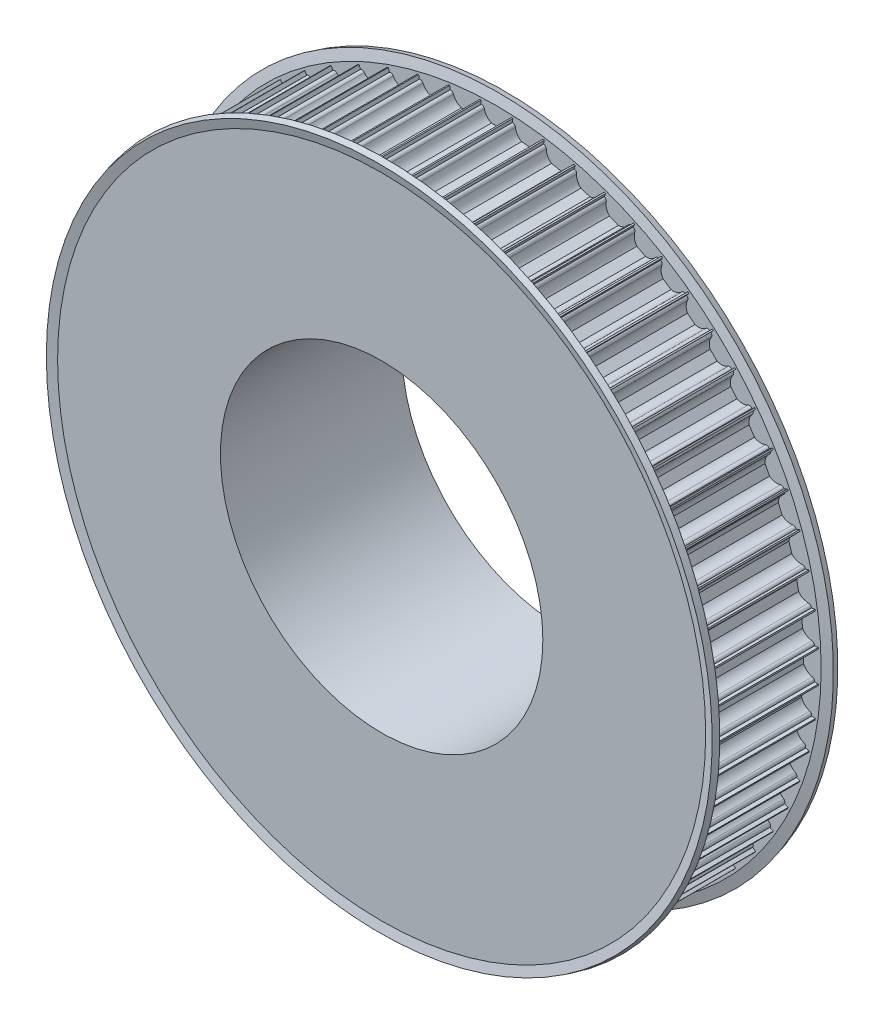
SolidWorks part; units mm, degrees
ref_plane "Front Plane" through (0, 0, 0) normal (0, 0, 1) x (1, 0, 0)
ref_plane "Top Plane" through (0, 0, 0) normal (0, 1, 0) x (1, 0, 0)
ref_plane "Right Plane" through (0, 0, 0) normal (1, 0, 0) x (0, 0, -1)
sketch "Sketch1" plane through (0, 0, 0) normal (1, 0, 0) x (0, 0, -1)
  line L0 (0, 0) -> (38.5259, 0) construction
  line L1 (0, 40) -> (45, 40)
  line L2 (45, 40) -> (45, 55.5)
  line L3 (45, 55.5) -> (30, 55.5)
  line L4 (30, 55.5) -> (30, 80)
  line L5 (30, 80) -> (0, 80)
  line L6 (0, 80) -> (0, 40)
  dimension "D1" = 80
  dimension "D2" = 40
  dimension "D3" = 30
  dimension "D4" = 15
  dimension "D5" = 15.5
revolve "Revolve1" add sketch "Sketch1" angle 360 about L0
sketch "Sketch2" plane through (0, 0, 0) normal (0, 0, 1) x (1, 0, 0)
  line L0 (-3.6742, 79) -> (-3.75, 79)
  line L1 (-3.75, 79) -> (-3.75, 81)
  line L2 (-3.75, 81) -> (3.75, 81)
  line L3 (3.75, 81) -> (3.75, 79)
  line L4 (3.6742, 79) -> (3.75, 79)
  line L5 (-1.199, 76.25) -> (1.199, 76.25)
  arc A0 (2.9394, 78.4) -> (1.199, 76.25) centre (0, 79) cw
  arc A1 (2.9394, 78.4) -> (3.6742, 79) centre (3.6742, 78.25) cw
  arc A2 (-2.9394, 78.4) -> (-3.6742, 79) centre (-3.6742, 78.25) ccw
  arc A3 (-1.199, 76.25) -> (-2.9394, 78.4) centre (0, 79) cw
  point P3 (0, 81)
  point P11 (3, 79)
  point P14 (-3, 79)
  dimension "D1" = 3
  dimension "D5" = 0.75
  dimension "D2" = 79
  dimension "D3" = 7.5
  dimension "D4" = 2
  dimension "D6" = 2.75
extrude "Cut-Extrude1" cut sketch "Sketch2" against normal up to next
pattern_circular "CirPattern1" count 64 over 360 about axis through (0, 0, 0) along (0, 0, 1) of "Cut-Extrude1"
sketch "Sketch3" plane through (0, 0, 0) normal (1, 0, 0) x (0, 0, -1)
  line L0 (15, -40.9775) -> (15, -11.3999) construction
  line L1 (30, -40.9775) -> (0, -40.9775) construction
  line L2 (30, -11.3999) -> (0, -11.3999) construction
  line L3 (30, 55.5) -> (30, 80.4056)
  line L4 (30, -32.718) -> (30, -30.2873) construction
  line L5 (30, -55.5) -> (30, 55.5) construction
  line L6 (30, 80.4056) -> (30.5902, 82.6081)
  line L7 (30.5902, 82.6081) -> (29.0902, 83.01)
  line L8 (29.0902, 83.01) -> (28.4471, 80.61)
  line L9 (28.4471, 80.61) -> (28.4471, 55.5)
  line L10 (28.4471, 55.5) -> (30, 55.5)
  line L11 (45, 55.5) -> (30, 55.5) construction
  line L12 (1.5529, 55.5) -> (0, 55.5)
  line L13 (1.5529, 80.61) -> (1.5529, 55.5)
  line L14 (0, 55.5) -> (0, 80.4056)
  line L15 (0, 80.4056) -> (-0.5902, 82.6081)
  line L16 (-0.5902, 82.6081) -> (0.9098, 83.01)
  line L17 (0.9098, 83.01) -> (1.5529, 80.61)
  line L18 (0, 0) -> (-11.2595, 0) construction
  dimension "D1" = 15
  dimension "D2" = 1.5
  dimension "D3" = 25.11
  dimension "D4" = 2.4
revolve "Revolve2" add sketch "Sketch3" angle 360 about L18
